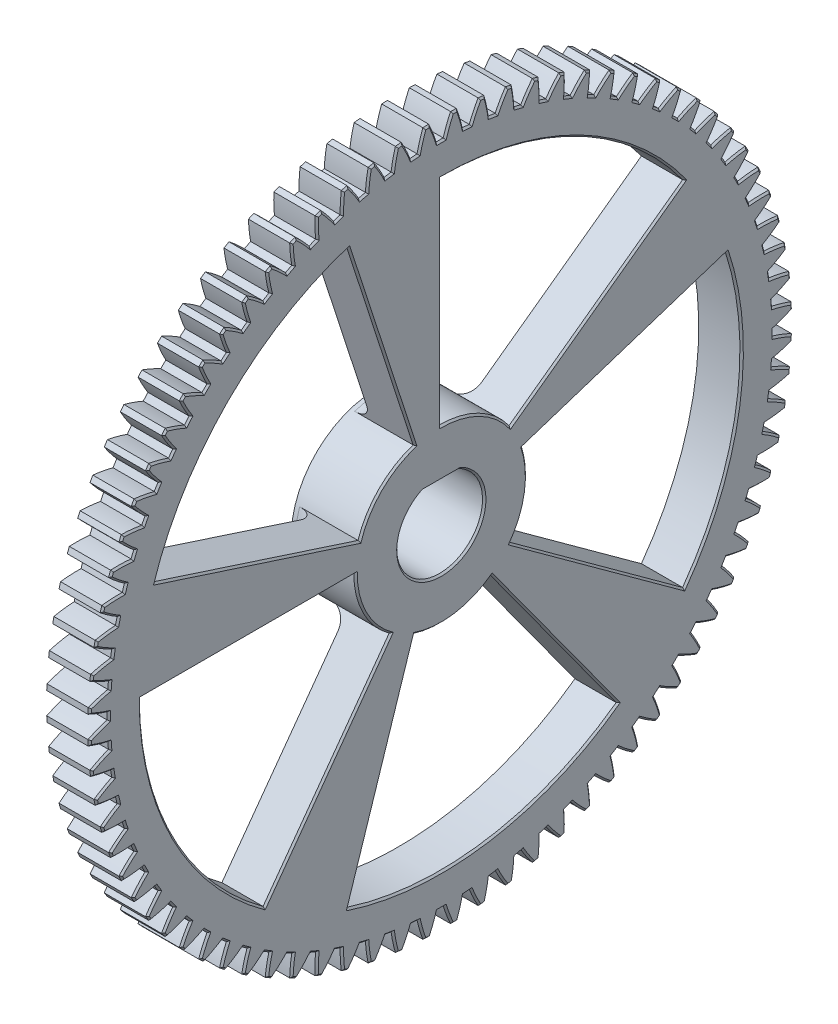
SolidWorks part; units mm, degrees
ref_plane "Plane1" through (0, 0, 0) normal (0, 0, 1) x (1, 0, 0)
ref_plane "Plane2" through (0, 0, 0) normal (0, 1, 0) x (1, 0, 0)
ref_plane "Plane3" through (0, 0, 0) normal (1, 0, 0) x (0, 0, -1)
other "Configuration Table"
sketch "HoldingSke" plane through (0, 0, 0) normal (0, 1, 0) x (1, 0, 0)
  line L0 (0, 0) -> (0.0868, -0.4924)
  line L1 (-15, 0) -> (100, 0) construction
  line L2 (0, 0) -> (-2.1039, 2.3779)
  line L3 (0, 0) -> (-11.863, 4.5341)
  line L4 (0, 0) -> (1.4996, 8.5048)
  line L5 (0, 0) -> (-14.0543, -5.2418)
  line L6 (0, 0) -> (-8.2896, -5.593)
  line L7 (-2.1039, 2.3779) -> (1.1249, 17.0263)
  line L8 (-76.2, 54.61) -> (-73.9, 54.61)
  line L9 (-71.009, 38.7566) -> (-53.1078, 45.2721)
  line L10 (-76.2, 71.12) -> (104.1128, 71.12)
  line L11 (0, 0) -> (-10, 0)
  line L12 (-76.2, 101.6) -> (-76.133, 101.6)
  line L13 (24.9733, 27.94) -> (52.9518, 28.4284)
  line L14 (24.9733, 27.94) -> (24.9743, 27.94)
  line L15 (24.9733, 27.94) -> (100.4006, 29.5858)
  line L16 (-63.627, -2) -> (-12.827, -2)
  circle A0 centre (0, 0) radius 6
  circle A1 centre (0, 0) radius 50
  circle A2 centre (0, 0) radius 50
  circle A3 centre (0, 0) radius 6
  dimension "Num_teeth" = 80
  dimension "Pitch_radius" = 180.3128
  dimension "Width" = 10
  dimension "Thickness" = 10
sketch "BasProSke" plane through (0, 0, 0) normal (0, 1, 0) x (1, 0, 0)
  line L0 (-10, 0) -> (60, 0) construction
  line L1 (0, 0) -> (0, 82)
  line L2 (0, 0) -> (10, 0)
  line L3 (10, 0) -> (10, 82)
  line L4 (10, 82) -> (0, 82)
  dimension "Thickness" = 10
  dimension "Diameter" = 164
revolve "Base-Revolve" add sketch "BasProSke" angle 360 about L0
sketch "TooCutSke" plane through (0, 0, 0) normal (1, 0, 0) x (0, 0, -1)
  line L1 (0, 0) -> (0, 107) construction
  line L2 (0, 0) -> (-1.6879, 79.9822) construction
  line L3 (0, 0) -> (-6.2805, 159.8503) construction
  line L4 (-1.6879, 79.9822) -> (-3.1403, 79.9251) construction
  arc A0 (0.8262, 77.4946) -> (-0.8262, 77.4946) centre (0, 0) ccw
  arc A1 (2.5557, 81.9856) -> (-2.5557, 81.9856) centre (0, 0) ccw
  circle A2 centre (0, 0) radius 80 construction
  circle A3 centre (0, 0) radius 75.1754 construction
  arc A4 (-0.8262, 77.4946) -> (-2.5557, 81.9856) centre (-31.4684, 68.2721) ccw
  arc A5 (2.5557, 81.9856) -> (0.8262, 77.4946) centre (31.4684, 68.2721) ccw
extrude "ToothCut" cut sketch "TooCutSke" along normal through all
fillet "Breaks" [suppressed] radius 0.04
fillet "RootFillets" [suppressed] radius 0.501
pattern_circular "TeethCuts" count 80 every 4.5 about axis through (-10, 0, 0) along (1, 0, 0) of "ToothCut", "RootFillets", "Breaks"
sketch "HubNeaOneSke" plane through (0, 0, 0) normal (-1, 0, 0) x (0, 0, 1)
  circle A0 centre (0, 0) radius 50
  dimension "Diameter" = 100
extrude "HubNearOne" add sketch "HubNeaOneSke" along normal blind 5.0001
sketch "HubNeaBotSke" plane through (0, 0, 0) normal (-1, 0, 0) x (0, 0, 1)
  circle A0 centre (0, 0) radius 50
  dimension "Diameter" = 100
extrude "HubNearBoth" [suppressed] add sketch "HubNeaBotSke" along normal blind 2.5
ref_plane "FarPln" through (10, 0, 0) normal (1, 0, 0) x (0, 0, -1)
sketch "HubFarSke" plane through (10, 0, 0) normal (1, 0, 0) x (0, 0, -1)
  circle A0 centre (0, 0) radius 50
  dimension "Diameter" = 100
extrude "HubFar" [suppressed] add sketch "HubFarSke" along normal blind 2.5
sketch "BorSke" plane through (0, 0, 0) normal (1, 0, 0) x (0, 0, -1)
  circle A0 centre (0, 0) radius 10
  dimension "Diameter" = 20
extrude "Bore" cut sketch "BorSke" along normal mid plane 30.0001
sketch "KeySke" plane through (0, 0, 0) normal (1, 0, 0) x (0, 0, -1)
  line L0 (-2.5, 0) -> (-2.5, 8.3)
  line L1 (-2.5, 8.3) -> (2.5, 8.3)
  line L2 (2.5, 8.3) -> (2.5, 0)
  line L3 (0, 0) -> (0, 34) construction
  line L4 (-2.5, 0) -> (2.5, 0)
  dimension "Width" = 5
extrude "Keyway" [suppressed] cut sketch "KeySke" along normal mid plane 30.0001
pattern_circular "Keyway2" [suppressed] count 2 every 90 about axis through (-10, 0, 0) along (1, 0, 0)
sketch "草图1" plane through (10, 0, 0) normal (1, 0, 0) x (0, 0, -1)
  line L0 (0, 20) -> (0, 70)
  line L1 (6.1803, 19.0211) -> (21.6312, 66.574)
  line L2 (11.7557, 16.1803) -> (41.145, 56.6312)
  line L3 (16.1803, 11.7557) -> (56.6312, 41.145)
  line L4 (19.0211, 6.1803) -> (66.574, 21.6312)
  line L5 (20, 0) -> (70, 0)
  line L6 (19.0211, -6.1803) -> (66.574, -21.6312)
  line L7 (16.1803, -11.7557) -> (56.6312, -41.145)
  line L8 (11.7557, -16.1803) -> (41.145, -56.6312)
  line L9 (6.1803, -19.0211) -> (21.6312, -66.574)
  line L10 (0, -20) -> (0, -70)
  line L11 (-6.1803, -19.0211) -> (-21.6312, -66.574)
  line L12 (-11.7557, -16.1803) -> (-41.145, -56.6312)
  line L13 (-16.1803, -11.7557) -> (-56.6312, -41.145)
  line L14 (-19.0211, -6.1803) -> (-66.574, -21.6312)
  line L15 (-20, 0) -> (-70, 0)
  line L16 (-19.0211, 6.1803) -> (-66.574, 21.6312)
  line L17 (-16.1803, 11.7557) -> (-56.6312, 41.145)
  line L18 (-11.7557, 16.1803) -> (-41.145, 56.6312)
  line L19 (-6.1803, 19.0211) -> (-21.6312, 66.574)
  circle A0 centre (0, 0) radius 20
  circle A1 centre (0, 0) radius 70
  point P47 (0, 0)
  dimension "D1" = 40
  dimension "D2" = 140
  dimension "D3" = 20
extrude "切除-拉伸1" cut sketch "草图1" against normal through all contours L1 A1 L0 A0 | L2 A1 L1 A0 | L3 A1 L2 A0 | L5 A1 L4 A0 | L6 A1 L5 A0 | L7 A1 L6 A0 | L9 A1 L8 A0 | L10 A1 L9 A0 | L11 A1 L10 A0 | L13 A1 L12 A0 | L14 A1 L13 A0 | L15 A1 L14 A0 | L17 A1 L16 A0 | L18 A1 L17 A0 | L19 A1 L18 A0
sketch "草图2" plane through (-5.0001, 0, 0) normal (-1, 0, 0) x (0, 0, 1)
  circle A0 centre (0, 0) radius 20
extrude "切除-拉伸2" cut sketch "草图2" against normal up to surface (5.0001 mm away) flip side to cut up to face at (0, 0, 0)
sketch "草图3" plane through (-5.0001, 0, 0) normal (-1, 0, 0) x (0, 0, 1)
  line L0 (-4.3589, 9) -> (4.3589, 9)
  arc A0 (4.3589, 9) -> (-4.3589, 9) centre (0, 0) ccw
  dimension "D2" = 20
  dimension "D1" = 9
extrude "凸台-拉伸1" add sketch "草图3" against normal up to surface (15.0001 mm away) up to face at (10, -6.6559, -42.0238)
chamfer "倒角1" distance 0.4 angle 45 342 edges at (10, -42.7975, 13.9058) (10, -69.1382, -10.9504) (10, -36.4058, -26.4503) (10, -19.7538, -3.1287) (10, 0, 45) (10, -31.7793, 62.3705) (10, -36.4058, 26.4503) (10, -9.0798, 17.8201) (10, 26.4503, -36.4058) (10, 62.3705, -31.7793) (10, 45, 0) (10, 17.8201, -9.0798) (10, 9, 0) (10, -10, 0) (10, 3.2193, 81.9368) (10, 4.6614, 79.6395) (10, 6.0805, 77.2601) (10, 7.8544, 79.3882) (10, 9.6381, 81.4316) (10, 10.8955, 79.0283) (10, 12.1235, 76.5449) (10, 14.0589, 78.5272) (10, 15.9974, 80.4244) (10, 17.0624, 77.9298) (10, 18.0918, 75.3577) (10, 20.1767, 77.1821) (10, 22.2581, 78.9213) (10, 23.1241, 76.3509) (10, 23.9485, 73.7059) (10, 26.1701, 75.3611) (10, 28.3816, 76.9317) (10, 29.0432, 74.3012) (10, 29.6576, 71.5997) (10, 32.0022, 73.0755) (10, 34.3301, 74.4677) (10, 34.7833, 71.7935) (10, 35.1838, 69.0521) (10, 37.637, 70.3394) (10, 40.0669, 71.5447) (10, 40.3089, 68.8431) (10, 40.4931, 66.0788) (10, 43.0398, 67.1696) (10, 45.5568, 68.1805) (10, 45.586, 65.4683) (10, 45.5528, 62.698) (10, 48.1772, 63.5857) (10, 50.7657, 64.396) (10, 50.5821, 61.6898) (10, 50.3316, 58.9307) (10, 53.0175, 59.6097) (10, 55.6617, 60.2144) (10, 55.2663, 57.531) (10, 54.8001, 54.8001) (10, 57.531, 55.2663) (10, 60.2144, 55.6617) (10, 59.6097, 53.0175) (10, 58.9307, 50.3316) (10, 61.6898, 50.5821) (10, 64.396, 50.7657) (10, 63.5857, 48.1772) (10, 62.698, 45.5528) (10, 65.4683, 45.586) (10, 68.1805, 45.5568) (10, 67.1696, 43.0398) (10, 66.0788, 40.4931) (10, 68.8431, 40.3089) (10, 71.5447, 40.0669) (10, 70.3394, 37.637) (10, 69.0521, 35.1838) (10, 71.7935, 34.7833) (10, 74.4677, 34.3301) (10, 73.0755, 32.0022) (10, 71.5997, 29.6576) (10, 74.3012, 29.0432) (10, 76.9317, 28.3816) (10, 75.3611, 26.1701) (10, 73.7059, 23.9485) (10, 76.3509, 23.1241) (10, 78.9213, 22.2581) (10, 77.1821, 20.1767) (10, 75.3577, 18.0918) (10, 77.9298, 17.0624) (10, 80.4244, 15.9974) (10, 78.5272, 14.0589) (10, 76.5449, 12.1235) (10, 79.0283, 10.8955) (10, 81.4316, 9.6381) (10, 79.3882, 7.8544) (10, 77.2601, 6.0805) (10, 79.6395, 4.6614) (10, 81.9368, 3.2193) (10, 79.7597, 1.6014) (10, 77.499, 0) (10, 79.7597, -1.6014) (10, 81.9368, -3.2193) (10, 79.6395, -4.6614) (10, 77.2601, -6.0805) (10, 79.3882, -7.8544) (10, 81.4316, -9.6381) (10, 79.0283, -10.8955) (10, 76.5449, -12.1235) (10, 78.5272, -14.0589) (10, 80.4244, -15.9974) (10, 77.9298, -17.0624) (10, 75.3577, -18.0918) (10, 77.1821, -20.1767) (10, 78.9213, -22.2581) (10, 76.3509, -23.1241) (10, 73.7059, -23.9485) (10, 75.3611, -26.1701) (10, 76.9317, -28.3816) (10, 74.3012, -29.0432) (10, 71.5997, -29.6576) (10, 73.0755, -32.0022) (10, 74.4677, -34.3301) (10, 71.7935, -34.7833) (10, 69.0521, -35.1838) (10, 70.3394, -37.637) (10, 71.5447, -40.0669) (10, 68.8431, -40.3089) (10, 66.0788, -40.4931) (10, 67.1696, -43.0398) (10, 68.1805, -45.5568) (10, 65.4683, -45.586) (10, 62.698, -45.5528) (10, 63.5857, -48.1772) (10, 64.396, -50.7657) (10, 61.6898, -50.5821) (10, 58.9307, -50.3316) (10, 59.6097, -53.0175) (10, 60.2144, -55.6617) (10, 57.531, -55.2663) (10, 54.8001, -54.8001) (10, 55.2663, -57.531) (10, 55.6617, -60.2144) (10, 53.0175, -59.6097) (10, 50.3316, -58.9307) (10, 50.5821, -61.6898) (10, 50.7657, -64.396) (10, 48.1772, -63.5857) (10, 45.5528, -62.698) (10, 45.586, -65.4683) (10, 45.5568, -68.1805) (10, 43.0398, -67.1696) (10, 40.4931, -66.0788) (10, 40.3089, -68.8431) (10, 40.0669, -71.5447) (10, 37.637, -70.3394) (10, 35.1838, -69.0521) (10, 34.7833, -71.7935) (10, 34.3301, -74.4677) (10, 32.0022, -73.0755) (10, 29.6576, -71.5997) (10, 29.0432, -74.3012) (10, 28.3816, -76.9317) (10, 26.1701, -75.3611) (10, 23.9485, -73.7059) (10, 23.1241, -76.3509) (10, 22.2581, -78.9213) (10, 20.1767, -77.1821) (10, 18.0918, -75.3577) (10, 17.0624, -77.9298) (10, 15.9974, -80.4244) (10, 14.0589, -78.5272) (10, 12.1235, -76.5449) (10, 10.8955, -79.0283) (10, 9.6381, -81.4316) (10, 7.8544, -79.3882) (10, 6.0805, -77.2601) (10, 4.6614, -79.6395) (10, 3.2193, -81.9368) (10, 1.6014, -79.7597) (10, 0, -77.499) (10, -1.6014, -79.7597) (10, -3.2193, -81.9368) (10, -4.6614, -79.6395) (10, -6.0805, -77.2601) (10, -7.8544, -79.3882) (10, -9.6381, -81.4316) (10, -10.8955, -79.0283) (10, -12.1235, -76.5449) (10, -14.0589, -78.5272) (10, -15.9974, -80.4244) (10, -17.0624, -77.9298) (10, -18.0918, -75.3577) (10, -20.1767, -77.1821) (10, -22.2581, -78.9213) (10, -23.1241, -76.3509) (10, -23.9485, -73.7059) (10, -26.1701, -75.3611) (10, -28.3816, -76.9317) (10, -29.0432, -74.3012) (10, -29.6576, -71.5997) (10, -32.0022, -73.0755) (10, -34.3301, -74.4677) (10, -34.7833, -71.7935) (10, -35.1838, -69.0521) (10, -37.637, -70.3394) (10, -40.0669, -71.5447) (10, -40.3089, -68.8431) (10, -40.4931, -66.0788) (10, -43.0398, -67.1696) (10, -45.5568, -68.1805) (10, -45.586, -65.4683) (10, -45.5528, -62.698) (10, -48.1772, -63.5857) (10, -50.7657, -64.396) (10, -50.5821, -61.6898) (10, -50.3316, -58.9307) (10, -53.0175, -59.6097) (10, -55.6617, -60.2144) (10, -55.2663, -57.531) (10, -54.8001, -54.8001) (10, -57.531, -55.2663) (10, -60.2144, -55.6617) (10, -59.6097, -53.0175) (10, -58.9307, -50.3316) (10, -61.6898, -50.5821) (10, -64.396, -50.7657) (10, -63.5857, -48.1772) (10, -62.698, -45.5528) (10, -65.4683, -45.586) (10, -68.1805, -45.5568) (10, -67.1696, -43.0398) (10, -66.0788, -40.4931) (10, -68.8431, -40.3089) (10, -71.5447, -40.0669) (10, -70.3394, -37.637) (10, -69.0521, -35.1838) (10, -71.7935, -34.7833) (10, -74.4677, -34.3301) (10, -73.0755, -32.0022) (10, -71.5997, -29.6576) (10, -74.3012, -29.0432) (10, -76.9317, -28.3816) (10, -75.3611, -26.1701) (10, -73.7059, -23.9485) (10, -76.3509, -23.1241) (10, -78.9213, -22.2581) (10, -77.1821, -20.1767) (10, -75.3577, -18.0918) (10, -77.9298, -17.0624) (10, -80.4244, -15.9974) (10, -78.5272, -14.0589) (10, -76.5449, -12.1235) (10, -79.0283, -10.8955) (10, -81.4316, -9.6381) (10, -79.3882, -7.8544) (10, -77.2601, -6.0805) (10, -79.6395, -4.6614) (10, -81.9368, -3.2193) (10, -79.7597, -1.6014) (10, -77.499, 0) (10, -79.7597, 1.6014) (10, -81.9368, 3.2193) (10, -79.6395, 4.6614) (10, -77.2601, 6.0805) (10, -79.3882, 7.8544) (10, -81.4316, 9.6381) (10, -79.0283, 10.8955) (10, -76.5449, 12.1235) (10, -78.5272, 14.0589) (10, -80.4244, 15.9974) (10, -77.9298, 17.0624) (10, -75.3577, 18.0918) (10, -77.1821, 20.1767) (10, -78.9213, 22.2581) (10, -76.3509, 23.1241) (10, -73.7059, 23.9485) (10, -75.3611, 26.1701) (10, -76.9317, 28.3816) (10, -74.3012, 29.0432) (10, -71.5997, 29.6576) (10, -73.0755, 32.0022) (10, -74.4677, 34.3301) (10, -71.7935, 34.7833) (10, -69.0521, 35.1838) (10, -70.3394, 37.637) (10, -71.5447, 40.0669) (10, -68.8431, 40.3089) (10, -66.0788, 40.4931) (10, -67.1696, 43.0398) (10, -68.1805, 45.5568) (10, -65.4683, 45.586) (10, -62.698, 45.5528) (10, -63.5857, 48.1772) (10, -64.396, 50.7657) (10, -61.6898, 50.5821) (10, -58.9307, 50.3316) (10, -59.6097, 53.0175) (10, -60.2144, 55.6617) (10, -57.531, 55.2663) (10, -54.8001, 54.8001) (10, -55.2663, 57.531) (10, -55.6617, 60.2144) (10, -53.0175, 59.6097) (10, -50.3316, 58.9307) (10, -50.5821, 61.6898) (10, -50.7657, 64.396) (10, -48.1772, 63.5857) (10, -45.5528, 62.698) (10, -45.586, 65.4683) (10, -45.5568, 68.1805) (10, -43.0398, 67.1696) (10, -40.4931, 66.0788) (10, -40.3089, 68.8431) (10, -40.0669, 71.5447) (10, -37.637, 70.3394) (10, -35.1838, 69.0521) (10, -34.7833, 71.7935) (10, -34.3301, 74.4677) (10, -32.0022, 73.0755) (10, -29.6576, 71.5997) (10, -29.0432, 74.3012) (10, -28.3816, 76.9317) (10, -26.1701, 75.3611) (10, -23.9485, 73.7059) (10, -23.1241, 76.3509) (10, -22.2581, 78.9213) (10, -20.1767, 77.1821) (10, -18.0918, 75.3577) (10, -17.0624, 77.9298) (10, -15.9974, 80.4244) (10, -14.0589, 78.5272) (10, -12.1235, 76.5449) (10, -10.8955, 79.0283) (10, -9.6381, 81.4316) (10, -7.8544, 79.3882) (10, -6.0805, 77.2601) (10, -4.6614, 79.6395) (10, -3.2193, 81.9368) (10, -1.6014, 79.7597) (10, 0, 77.499) (10, 1.6014, 79.7597) (10, 42.7975, 13.9058) (10, 49.4975, 49.4975) (10, 13.9058, 42.7975) (10, 14.1421, 14.1421) (10, -26.4503, -36.4058) (10, -10.9504, -69.1382) (10, 13.9058, -42.7975) (10, -3.1287, -19.7538)
fillet "圆角1" radius 4 5 edges at (0, 19.7538, 3.1287) (0, 3.1287, 19.7538) (0, -17.8201, 9.0798) (0, -14.1421, -14.1421) (0, 9.0798, -17.8201)
equation "' \"Module@HoldingSke\" = 6.35"
equation "' \"Num_teeth@HoldingSke\" = 12"
equation "' \"Ap@HoldingSke\" =  20"
equation "' \"Ap@HoldingSke\" = 20"
equation "' \"Width@HoldingSke\" = 0.5 * 25.4"
equation "' \"Hub_dia@HoldingSke\"= 1 * 25.4"
equation "' \"Hub_dia@HoldingSke\" = 1 * 25.4"
equation "' \"Overall_len@HoldingSke\" = 1.0 * 25.4"
equation "' \"Bore@HoldingSke\" = 0.75 * 25.4"
equation "' \"T_dim@HoldingSke\" = 0.1 * 25.4"
equation "' \"Width@KeySke\" = 0.25 * 25.4"
equation "' \"Show_teeth@HoldingSke\" = 13"
equation "' \"Backlash@HoldingSke\" = 0.009 * 25.4"
equation "' \"Addendum_fac@HoldingSke\" = 1.0"
equation "' \"Dedendum_fac@HoldingSke\" = 1.25"
equation "' \"Dedendum_add@HoldingSke\" = 0.00005 * 25.4"
equation "' \"Clearance_fac@HoldingSke\" = 0.25"
equation "\"Pitch@HoldingSke\" = 1 / \"Module@HoldingSke\""
equation "\"Overcut_dia@TooCutSke\" = (\"Num_teeth@HoldingSke\" + 2 * \"Addendum_fac@HoldingSke\") / \"Pitch@HoldingSke\" + 0.002 * 25.4"
equation "\"Pitch_dia@TooCutSke\" = \"Num_teeth@HoldingSke\" / \"Pitch@HoldingSke\""
equation "\"Base_dia@TooCutSke\" = \"Num_teeth@HoldingSke\" / \"Pitch@HoldingSke\" * cos((\"Ap@HoldingSke\"  * 3.14159265 / 180))"
equation "\"Root_dia@TooCutSke\" = (\"Num_teeth@HoldingSke\" + 2) / \"Pitch@HoldingSke\" - 2 * (\"Addendum_fac@HoldingSke\" + \"Dedendum_fac@HoldingSke\") / \"Pitch@HoldingSke\" - \"Dedendum_add@HoldingSke\" * 2"
equation "\"Half_ang@TooCutSke\" = 180 / \"Num_teeth@HoldingSke\""
equation "\"Half_CT@TooCutSke\" = \"Num_teeth@HoldingSke\" / \"Pitch@HoldingSke\" * sin((3.14159265 / 2 / \"Num_teeth@HoldingSke\")) / 2 - 7 * \"Backlash@HoldingSke\" / 4"
equation "\"Flank_rad@TooCutSke\" = \"Num_teeth@HoldingSke\" / \"Pitch@HoldingSke\" / 5"
equation "\"Radius@RootFillets\" = \"Clearance_fac@HoldingSke\" / \"Pitch@HoldingSke\" + \"Dedendum_add@HoldingSke\""
equation "\"Break_rad@Breaks\" = 0.02 / \"Pitch@HoldingSke\""
equation "\"Thickness@HoldingSke\" = \"Width@HoldingSke\""
equation "\"OAL@HoldingSke\" = \"Thickness@HoldingSke\""
equation "\"MHD@HoldingSke\" = (\"Num_teeth@HoldingSke\" + 2) / \"Pitch@HoldingSke\" - 2 * (\"Addendum_fac@HoldingSke\" + \"Dedendum_fac@HoldingSke\")  / \"Pitch@HoldingSke\" - \"Dedendum_add@HoldingSke\" * 2"
equation "\"MBD@HoldingSke\" = (\"Num_teeth@HoldingSke\" + 2) / \"Pitch@HoldingSke\" - 2 * (\"Addendum_fac@HoldingSke\" + \"Dedendum_fac@HoldingSke\")  / \"Pitch@HoldingSke\" - \"Dedendum_add@HoldingSke\" * 2 - 0.002 * 25.4"
equation "\"MHD@HoldingSke\" = ((sgn( \"MHD@HoldingSke\" - \"Hub_dia@HoldingSke\" )-1)*( \"MHD@HoldingSke\" - \"Hub_dia@HoldingSke\" ))/-2+ \"Hub_dia@HoldingSke\""
equation "\"MBD@HoldingSke\" = ((sgn( \"MBD@HoldingSke\" - \"Bore@HoldingSke\" )-1)*( \"MBD@HoldingSke\" - \"Bore@HoldingSke\" ))/-2+ \"Bore@HoldingSke\""
equation "\"OAL@HoldingSke\" = ((sgn( \"OAL@HoldingSke\" - \"Overall_len@HoldingSke\" )+1)*( \"OAL@HoldingSke\" - \"Overall_len@HoldingSke\" ))/2 + \"Overall_len@HoldingSke\" + 0.000002 * 25.4"
equation "\"Num_teeth@TeethCuts\" = int( \"Show_teeth@HoldingSke\" ) + 1"
equation "\"Num_teeth@TeethCuts\" = ((sgn( \"Num_teeth@TeethCuts\" - \"Num_teeth@HoldingSke\" )-1)*( \"Num_teeth@TeethCuts\" - \"Num_teeth@HoldingSke\" ))/-2+ \"Num_teeth@HoldingSke\""
equation "\"Num_teeth@TeethCuts\" = ((sgn( \"Num_teeth@TeethCuts\" - 2.0)+1)*( \"Num_teeth@TeethCuts\" - 2.0))/2 +2.0"
equation "\"Angle@TeethCuts\" = 360.0 / \"Num_teeth@HoldingSke\""
equation "\"Diameter@BasProSke\" = (\"Num_teeth@HoldingSke\" + 2 * \"Addendum_fac@HoldingSke\") / \"Pitch@HoldingSke\""
equation "\"Thickness@BasProSke\"  = \"Thickness@HoldingSke\""
equation "' \"Fillet_rad@BasProSke\" =  \"Thickness@HoldingSke\" * 0.05"
equation "' \"Fillet_rad@BasProSke\" = \"Thickness@HoldingSke\" * 0.05"
equation "\"MHD@HoldingSke\" = ((sgn( \"MHD@HoldingSke\" - \"Root_dia@TooCutSke\" )-1)*( \"MHD@HoldingSke\" - \"Root_dia@TooCutSke\" ))/-2+ \"Root_dia@TooCutSke\""
equation "\"Diameter@HubNeaOneSke\" = \"MHD@HoldingSke\""
equation "\"Length@HubNearOne\" = \"OAL@HoldingSke\" - \"Thickness@BasProSke\""
equation "\"Diameter@HubNeaBotSke\" = \"MHD@HoldingSke\""
equation "\"Length@HubNearBoth\" = ( \"OAL@HoldingSke\" - \"Thickness@BasProSke\" ) / 2.0"
equation "\"Thickness@FarPln\" = \"Thickness@BasProSke\""
equation "\"Diameter@HubFarSke\" = \"MHD@HoldingSke\""
equation "\"Length@HubFar\" = ( \"OAL@HoldingSke\" - \"Thickness@BasProSke\" ) / 2.0"
equation "\"Diameter@BorSke\"=20"
equation "\"D1@Bore\" = \"OAL@HoldingSke\" * 2.0"
equation "\"D1@Keyway\" = \"OAL@HoldingSke\" * 2.0"
equation "\"Offset@KeySke\" = \"T_dim@HoldingSke\" + \"MBD@HoldingSke\" / 2.0"
